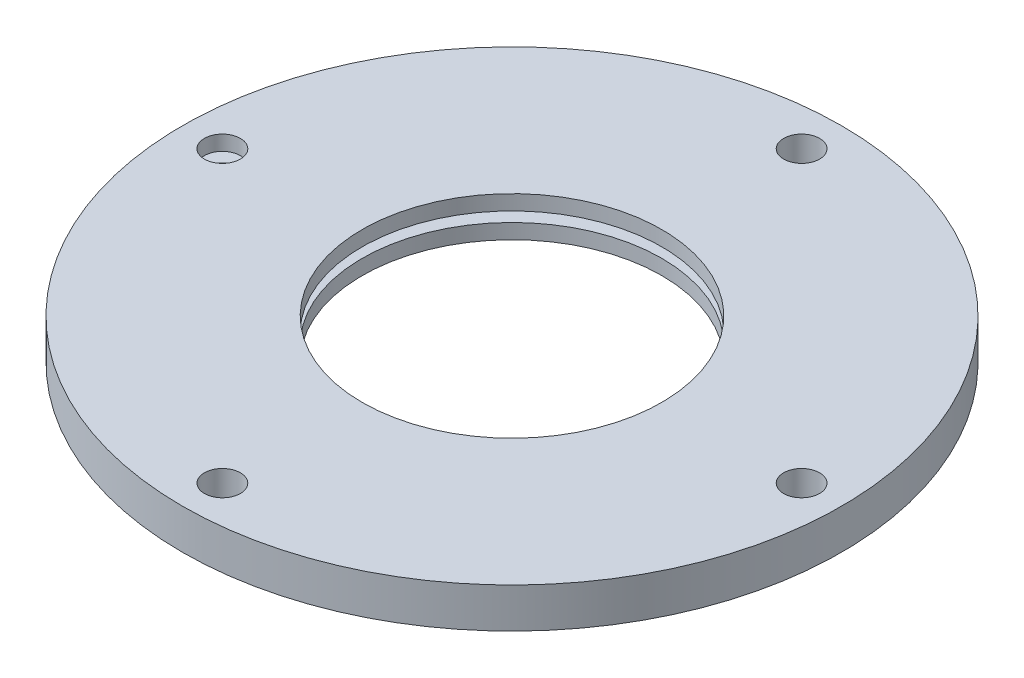
SolidWorks part; units mm, degrees
material "ABS"
ref_plane "Front Plane" through (0, 0, 0) normal (0, 0, 1) x (1, 0, 0)
ref_plane "Top Plane" through (0, 0, 0) normal (0, 1, 0) x (1, 0, 0)
ref_plane "Right Plane" through (0, 0, 0) normal (1, 0, 0) x (0, 0, -1)
sketch "Sketch1" plane through (0, 0, 0) normal (0, 1, 0) x (1, 0, 0)
  circle A0 centre (0, 0) radius 33
  circle A1 centre (-29, 0) radius 1.5
  circle A2 centre (0, 0) radius 29 construction
  circle A3 centre (0, 29) radius 1.5
  circle A4 centre (29, 0) radius 1.5
  circle A5 centre (0, -29) radius 1.5
  point P15 (0, 0)
  dimension "D1" = 66
  dimension "D2" = 4
  dimension "D3" = 3
  dimension "D4" = 4
extrude "Boss-Extrude1" add sketch "Sketch1" along normal blind 4
hole_wizard "CSK for M3 Flat Head Machine Screw1" positions "Sketch2" profile "Sketch3" countersink size "M3" standard "ANSI Metric" end condition through all
sketch "Sketch2" plane through (0, 0, 0) normal (0, -1, 0) x (-1, 0, 0)
  point P0 (0, -29)
  point P3 (29, 0)
  point P6 (0, 29)
  point P9 (-29, 0)
sketch "Sketch3" plane through (0, 0, 29) normal (1, 0, 0) x (0, 0, -1)
  line L0 (0, 0) -> (0, 4)
  line L1 (0, 4) -> (1.8, 4)
  line L2 (1.8, 4) -> (1.8, 1.35)
  line L3 (1.8, 1.35) -> (3.15, 0)
  line L5 (3.15, 0) -> (0, 0)
  line L6 (-1.8, 1.35) -> (-3.15, 0) construction
  line L11 (0, -6.35) -> (0, 107.95) construction
  dimension "Thru Hole Dia." = 3.6
  dimension "Thru Hole Depth" = 4
  dimension "Near C'Sink Dia." = 6.3
  dimension "Near C'Sink Angle" = 90
sketch "Croquis1" plane through (0, 0, 0) normal (0, -1, 0) x (1, 0, 0)
  circle A0 centre (0, 0) radius 15
  dimension "D1" = 30
extrude "Cortar-Extruir1" cut sketch "Croquis1" against normal up to next
ref_axis "Eje1" through (0, 4, 0) along (0, -1, 0)
ref_plane "Plano1" through (-33, 0, 0) normal (-1, 0, 0) x (0, 0, 1)
sketch "Croquis2" plane through (-33, 0, 0) normal (-1, 0, 0) x (0, 0, 1)
  line L0 (0, 0) -> (0, 4) construction
  line L1 (0, 4) -> (0, 0) construction
  line L3 (-20, 2.5) -> (20, 2.5)
  line L4 (-20, 2.5) -> (-20, 1.5)
  line L5 (-20, 1.5) -> (20, 1.5)
  line L6 (20, 2.5) -> (20, 1.5)
  line L7 (-20, 2.5) -> (20, 1.5) construction
  line L8 (-20, 1.5) -> (20, 2.5) construction
  line L10 (-33, 0) -> (33, 0) construction
  line L11 (33, 4) -> (-33, 4) construction
  point P5 (0, 2)
  dimension "D1" = 40
  dimension "D2" = 1
  dimension "D3" = 1.5
  dimension "D4" = 1.5
extrude "Cortar-Extruir2" cut sketch "Croquis2" against normal blind 50
